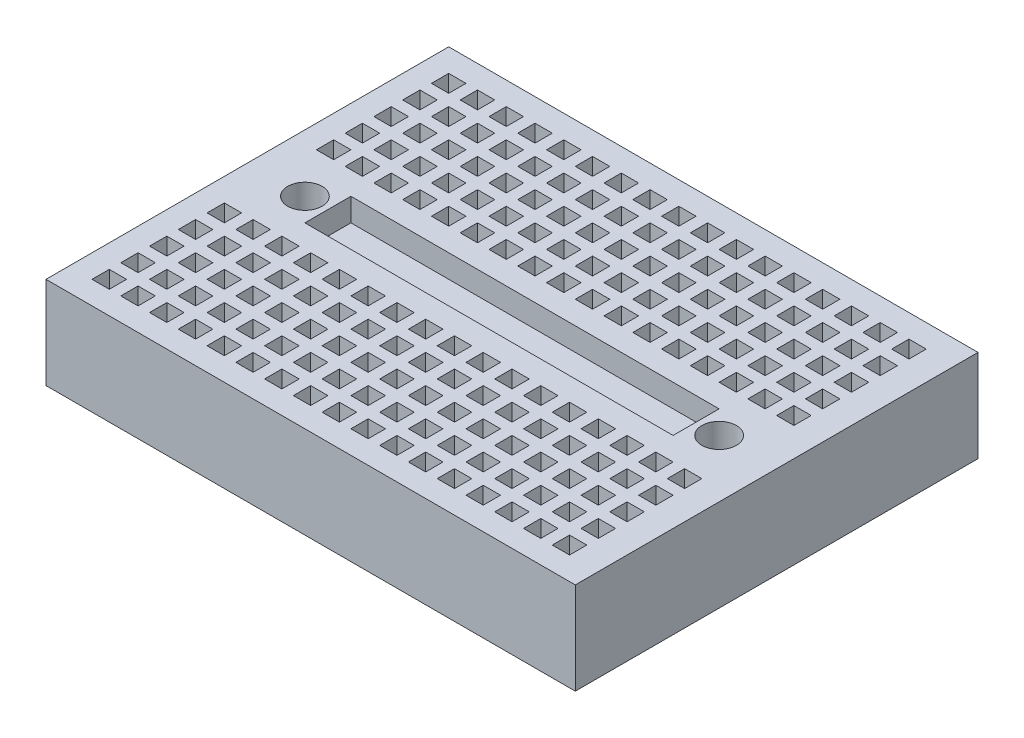
SolidWorks part; units mm, degrees
ref_plane "Front Plane" through (0, 0, 0) normal (0, 0, 1) x (1, 0, 0)
ref_plane "Top Plane" through (0, 0, 0) normal (0, 1, 0) x (1, 0, 0)
ref_plane "Right Plane" through (0, 0, 0) normal (1, 0, 0) x (0, 0, -1)
sketch "Sketch1" plane through (0, 0, 0) normal (0, 1, 0) x (1, 0, 0)
  line L1 (23, -17.5) -> (-23, -17.5)
  line L2 (23, -17.5) -> (23, 17.5)
  line L3 (23, 17.5) -> (-23, 17.5)
  line L4 (-23, -17.5) -> (-23, 17.5)
  line L5 (23, -17.5) -> (-23, 17.5) construction
  line L6 (23, 17.5) -> (-23, -17.5) construction
  circle A0 centre (18, 0) radius 1.5
  circle A1 centre (-18, 0) radius 1.5
  point P0 (0, 0)
  point P11 (-18, 0)
  dimension "D3" = 3
  dimension "D4" = 3
  dimension "D1" = 46
  dimension "D2" = 35
  dimension "D5" = 5
  dimension "D6" = 5
extrude "Boss-Extrude1" add sketch "Sketch1" along normal blind 8
sketch "Sketch2" plane through (0, 8, 0) normal (0, 1, 0) x (1, 0, 0)
  line L1 (16, -2) -> (-16, -2)
  line L2 (16, -2) -> (16, 2)
  line L3 (16, 2) -> (-16, 2)
  line L4 (-16, -2) -> (-16, 2)
  line L5 (16, -2) -> (-16, 2) construction
  line L6 (16, 2) -> (-16, -2) construction
  circle A0 centre (-18, 0) radius 1.5 construction
  point P0 (0, 0)
  dimension "D1" = 4
  dimension "D2" = 2
extrude "Cut-Extrude1" cut sketch "Sketch2" against normal blind 2
sketch "Sketch3" plane through (0, 8, 0) normal (0, 1, 0) x (1, 0, 0)
  line L0 (23, 17.5) -> (-23, 17.5) construction
  line L1 (-21, 15.5) -> (-19.5, 15.5)
  line L2 (-21, 15.5) -> (-21, 14)
  line L3 (-21, 14) -> (-19.5, 14)
  line L4 (-19.5, 15.5) -> (-19.5, 14)
  line L5 (-21, 15.5) -> (-19.5, 14) construction
  line L6 (-21, 14) -> (-19.5, 15.5) construction
  line L7 (-23, 17.5) -> (-23, -17.5) construction
  line L8 (-18.5, 15.5) -> (-17, 15.5)
  line L9 (-18.5, 15.5) -> (-18.5, 14)
  line L10 (-17, 15.5) -> (-17, 14)
  line L11 (-18.5, 14) -> (-17, 14)
  line L12 (-16, 15.5) -> (-14.5, 15.5)
  line L13 (-16, 15.5) -> (-16, 14)
  line L14 (-14.5, 15.5) -> (-14.5, 14)
  line L15 (-16, 14) -> (-14.5, 14)
  line L16 (-13.5, 15.5) -> (-12, 15.5)
  line L17 (-13.5, 15.5) -> (-13.5, 14)
  line L18 (-12, 15.5) -> (-12, 14)
  line L19 (-13.5, 14) -> (-12, 14)
  line L20 (-11, 15.5) -> (-9.5, 15.5)
  line L21 (-11, 15.5) -> (-11, 14)
  line L22 (-9.5, 15.5) -> (-9.5, 14)
  line L23 (-11, 14) -> (-9.5, 14)
  line L24 (-8.5, 15.5) -> (-7, 15.5)
  line L25 (-8.5, 15.5) -> (-8.5, 14)
  line L26 (-7, 15.5) -> (-7, 14)
  line L27 (-8.5, 14) -> (-7, 14)
  line L28 (-6, 15.5) -> (-4.5, 15.5)
  line L29 (-6, 15.5) -> (-6, 14)
  line L30 (-4.5, 15.5) -> (-4.5, 14)
  line L31 (-6, 14) -> (-4.5, 14)
  line L32 (-3.5, 15.5) -> (-2, 15.5)
  line L33 (-3.5, 15.5) -> (-3.5, 14)
  line L34 (-2, 15.5) -> (-2, 14)
  line L35 (-3.5, 14) -> (-2, 14)
  line L36 (-1, 15.5) -> (0.5, 15.5)
  line L37 (-1, 15.5) -> (-1, 14)
  line L38 (0.5, 15.5) -> (0.5, 14)
  line L39 (-1, 14) -> (0.5, 14)
  line L40 (1.5, 15.5) -> (3, 15.5)
  line L41 (1.5, 15.5) -> (1.5, 14)
  line L42 (3, 15.5) -> (3, 14)
  line L43 (1.5, 14) -> (3, 14)
  line L44 (4, 15.5) -> (5.5, 15.5)
  line L45 (4, 15.5) -> (4, 14)
  line L46 (5.5, 15.5) -> (5.5, 14)
  line L47 (4, 14) -> (5.5, 14)
  line L48 (6.5, 15.5) -> (8, 15.5)
  line L49 (6.5, 15.5) -> (6.5, 14)
  line L50 (8, 15.5) -> (8, 14)
  line L51 (6.5, 14) -> (8, 14)
  line L52 (9, 15.5) -> (10.5, 15.5)
  line L53 (9, 15.5) -> (9, 14)
  line L54 (10.5, 15.5) -> (10.5, 14)
  line L55 (9, 14) -> (10.5, 14)
  line L56 (11.5, 15.5) -> (13, 15.5)
  line L57 (11.5, 15.5) -> (11.5, 14)
  line L58 (13, 15.5) -> (13, 14)
  line L59 (11.5, 14) -> (13, 14)
  line L60 (14, 15.5) -> (15.5, 15.5)
  line L61 (14, 15.5) -> (14, 14)
  line L62 (15.5, 15.5) -> (15.5, 14)
  line L63 (14, 14) -> (15.5, 14)
  line L64 (16.5, 15.5) -> (18, 15.5)
  line L65 (16.5, 15.5) -> (16.5, 14)
  line L66 (18, 15.5) -> (18, 14)
  line L67 (16.5, 14) -> (18, 14)
  line L68 (19, 15.5) -> (20.5, 15.5)
  line L69 (19, 15.5) -> (19, 14)
  line L70 (20.5, 15.5) -> (20.5, 14)
  line L71 (19, 14) -> (20.5, 14)
  line L72 (-18.5, 13) -> (-17, 13)
  line L73 (-18.5, 13) -> (-18.5, 11.5)
  line L74 (-17, 13) -> (-17, 11.5)
  line L75 (-18.5, 11.5) -> (-17, 11.5)
  line L76 (-16, 13) -> (-14.5, 13)
  line L77 (-16, 13) -> (-16, 11.5)
  line L78 (-14.5, 13) -> (-14.5, 11.5)
  line L79 (-16, 11.5) -> (-14.5, 11.5)
  line L80 (-13.5, 13) -> (-12, 13)
  line L81 (-13.5, 13) -> (-13.5, 11.5)
  line L82 (-12, 13) -> (-12, 11.5)
  line L83 (-13.5, 11.5) -> (-12, 11.5)
  line L84 (-11, 13) -> (-9.5, 13)
  line L85 (-11, 13) -> (-11, 11.5)
  line L86 (-9.5, 13) -> (-9.5, 11.5)
  line L87 (-11, 11.5) -> (-9.5, 11.5)
  line L88 (-8.5, 13) -> (-7, 13)
  line L89 (-8.5, 13) -> (-8.5, 11.5)
  line L90 (-7, 13) -> (-7, 11.5)
  line L91 (-8.5, 11.5) -> (-7, 11.5)
  line L92 (-6, 13) -> (-4.5, 13)
  line L93 (-6, 13) -> (-6, 11.5)
  line L94 (-4.5, 13) -> (-4.5, 11.5)
  line L95 (-6, 11.5) -> (-4.5, 11.5)
  line L96 (-3.5, 13) -> (-2, 13)
  line L97 (-3.5, 13) -> (-3.5, 11.5)
  line L98 (-2, 13) -> (-2, 11.5)
  line L99 (-3.5, 11.5) -> (-2, 11.5)
  line L100 (-1, 13) -> (0.5, 13)
  line L101 (-1, 13) -> (-1, 11.5)
  line L102 (0.5, 13) -> (0.5, 11.5)
  line L103 (-1, 11.5) -> (0.5, 11.5)
  line L104 (1.5, 13) -> (3, 13)
  line L105 (1.5, 13) -> (1.5, 11.5)
  line L106 (3, 13) -> (3, 11.5)
  line L107 (1.5, 11.5) -> (3, 11.5)
  line L108 (4, 13) -> (5.5, 13)
  line L109 (4, 13) -> (4, 11.5)
  line L110 (5.5, 13) -> (5.5, 11.5)
  line L111 (4, 11.5) -> (5.5, 11.5)
  line L112 (6.5, 13) -> (8, 13)
  line L113 (6.5, 13) -> (6.5, 11.5)
  line L114 (8, 13) -> (8, 11.5)
  line L115 (6.5, 11.5) -> (8, 11.5)
  line L116 (9, 13) -> (10.5, 13)
  line L117 (9, 13) -> (9, 11.5)
  line L118 (10.5, 13) -> (10.5, 11.5)
  line L119 (9, 11.5) -> (10.5, 11.5)
  line L120 (11.5, 13) -> (13, 13)
  line L121 (11.5, 13) -> (11.5, 11.5)
  line L122 (13, 13) -> (13, 11.5)
  line L123 (11.5, 11.5) -> (13, 11.5)
  line L124 (14, 13) -> (15.5, 13)
  line L125 (14, 13) -> (14, 11.5)
  line L126 (15.5, 13) -> (15.5, 11.5)
  line L127 (14, 11.5) -> (15.5, 11.5)
  line L128 (16.5, 13) -> (18, 13)
  line L129 (16.5, 13) -> (16.5, 11.5)
  line L130 (18, 13) -> (18, 11.5)
  line L131 (16.5, 11.5) -> (18, 11.5)
  line L132 (19, 13) -> (20.5, 13)
  line L133 (19, 13) -> (19, 11.5)
  line L134 (20.5, 13) -> (20.5, 11.5)
  line L135 (19, 11.5) -> (20.5, 11.5)
  line L136 (-18.5, 10.5) -> (-17, 10.5)
  line L137 (-18.5, 10.5) -> (-18.5, 9)
  line L138 (-17, 10.5) -> (-17, 9)
  line L139 (-18.5, 9) -> (-17, 9)
  line L140 (-16, 10.5) -> (-14.5, 10.5)
  line L141 (-16, 10.5) -> (-16, 9)
  line L142 (-14.5, 10.5) -> (-14.5, 9)
  line L143 (-16, 9) -> (-14.5, 9)
  line L144 (-13.5, 10.5) -> (-12, 10.5)
  line L145 (-13.5, 10.5) -> (-13.5, 9)
  line L146 (-12, 10.5) -> (-12, 9)
  line L147 (-13.5, 9) -> (-12, 9)
  line L148 (-11, 10.5) -> (-9.5, 10.5)
  line L149 (-11, 10.5) -> (-11, 9)
  line L150 (-9.5, 10.5) -> (-9.5, 9)
  line L151 (-11, 9) -> (-9.5, 9)
  line L152 (-8.5, 10.5) -> (-7, 10.5)
  line L153 (-8.5, 10.5) -> (-8.5, 9)
  line L154 (-7, 10.5) -> (-7, 9)
  line L155 (-8.5, 9) -> (-7, 9)
  line L156 (-6, 10.5) -> (-4.5, 10.5)
  line L157 (-6, 10.5) -> (-6, 9)
  line L158 (-4.5, 10.5) -> (-4.5, 9)
  line L159 (-6, 9) -> (-4.5, 9)
  line L160 (-3.5, 10.5) -> (-2, 10.5)
  line L161 (-3.5, 10.5) -> (-3.5, 9)
  line L162 (-2, 10.5) -> (-2, 9)
  line L163 (-3.5, 9) -> (-2, 9)
  line L164 (-1, 10.5) -> (0.5, 10.5)
  line L165 (-1, 10.5) -> (-1, 9)
  line L166 (0.5, 10.5) -> (0.5, 9)
  line L167 (-1, 9) -> (0.5, 9)
  line L168 (1.5, 10.5) -> (3, 10.5)
  line L169 (1.5, 10.5) -> (1.5, 9)
  line L170 (3, 10.5) -> (3, 9)
  line L171 (1.5, 9) -> (3, 9)
  line L172 (4, 10.5) -> (5.5, 10.5)
  line L173 (4, 10.5) -> (4, 9)
  line L174 (5.5, 10.5) -> (5.5, 9)
  line L175 (4, 9) -> (5.5, 9)
  line L176 (6.5, 10.5) -> (8, 10.5)
  line L177 (6.5, 10.5) -> (6.5, 9)
  line L178 (8, 10.5) -> (8, 9)
  line L179 (6.5, 9) -> (8, 9)
  line L180 (9, 10.5) -> (10.5, 10.5)
  line L181 (9, 10.5) -> (9, 9)
  line L182 (10.5, 10.5) -> (10.5, 9)
  line L183 (9, 9) -> (10.5, 9)
  line L184 (11.5, 10.5) -> (13, 10.5)
  line L185 (11.5, 10.5) -> (11.5, 9)
  line L186 (13, 10.5) -> (13, 9)
  line L187 (11.5, 9) -> (13, 9)
  line L188 (14, 10.5) -> (15.5, 10.5)
  line L189 (14, 10.5) -> (14, 9)
  line L190 (15.5, 10.5) -> (15.5, 9)
  line L191 (14, 9) -> (15.5, 9)
  line L192 (16.5, 10.5) -> (18, 10.5)
  line L193 (16.5, 10.5) -> (16.5, 9)
  line L194 (18, 10.5) -> (18, 9)
  line L195 (16.5, 9) -> (18, 9)
  line L196 (19, 10.5) -> (20.5, 10.5)
  line L197 (19, 10.5) -> (19, 9)
  line L198 (20.5, 10.5) -> (20.5, 9)
  line L199 (19, 9) -> (20.5, 9)
  line L200 (-18.5, 8) -> (-17, 8)
  line L201 (-18.5, 8) -> (-18.5, 6.5)
  line L202 (-17, 8) -> (-17, 6.5)
  line L203 (-18.5, 6.5) -> (-17, 6.5)
  line L204 (-16, 8) -> (-14.5, 8)
  line L205 (-16, 8) -> (-16, 6.5)
  line L206 (-14.5, 8) -> (-14.5, 6.5)
  line L207 (-16, 6.5) -> (-14.5, 6.5)
  line L208 (-13.5, 8) -> (-12, 8)
  line L209 (-13.5, 8) -> (-13.5, 6.5)
  line L210 (-12, 8) -> (-12, 6.5)
  line L211 (-13.5, 6.5) -> (-12, 6.5)
  line L212 (-11, 8) -> (-9.5, 8)
  line L213 (-11, 8) -> (-11, 6.5)
  line L214 (-9.5, 8) -> (-9.5, 6.5)
  line L215 (-11, 6.5) -> (-9.5, 6.5)
  line L216 (-8.5, 8) -> (-7, 8)
  line L217 (-8.5, 8) -> (-8.5, 6.5)
  line L218 (-7, 8) -> (-7, 6.5)
  line L219 (-8.5, 6.5) -> (-7, 6.5)
  line L220 (-6, 8) -> (-4.5, 8)
  line L221 (-6, 8) -> (-6, 6.5)
  line L222 (-4.5, 8) -> (-4.5, 6.5)
  line L223 (-6, 6.5) -> (-4.5, 6.5)
  line L224 (-3.5, 8) -> (-2, 8)
  line L225 (-3.5, 8) -> (-3.5, 6.5)
  line L226 (-2, 8) -> (-2, 6.5)
  line L227 (-3.5, 6.5) -> (-2, 6.5)
  line L228 (-1, 8) -> (0.5, 8)
  line L229 (-1, 8) -> (-1, 6.5)
  line L230 (0.5, 8) -> (0.5, 6.5)
  line L231 (-1, 6.5) -> (0.5, 6.5)
  line L232 (1.5, 8) -> (3, 8)
  line L233 (1.5, 8) -> (1.5, 6.5)
  line L234 (3, 8) -> (3, 6.5)
  line L235 (1.5, 6.5) -> (3, 6.5)
  line L236 (4, 8) -> (5.5, 8)
  line L237 (4, 8) -> (4, 6.5)
  line L238 (5.5, 8) -> (5.5, 6.5)
  line L239 (4, 6.5) -> (5.5, 6.5)
  line L240 (6.5, 8) -> (8, 8)
  line L241 (6.5, 8) -> (6.5, 6.5)
  line L242 (8, 8) -> (8, 6.5)
  line L243 (6.5, 6.5) -> (8, 6.5)
  line L244 (9, 8) -> (10.5, 8)
  line L245 (9, 8) -> (9, 6.5)
  line L246 (10.5, 8) -> (10.5, 6.5)
  line L247 (9, 6.5) -> (10.5, 6.5)
  line L248 (11.5, 8) -> (13, 8)
  line L249 (11.5, 8) -> (11.5, 6.5)
  line L250 (13, 8) -> (13, 6.5)
  line L251 (11.5, 6.5) -> (13, 6.5)
  line L252 (14, 8) -> (15.5, 8)
  line L253 (14, 8) -> (14, 6.5)
  line L254 (15.5, 8) -> (15.5, 6.5)
  line L255 (14, 6.5) -> (15.5, 6.5)
  line L256 (16.5, 8) -> (18, 8)
  line L257 (16.5, 8) -> (16.5, 6.5)
  line L258 (18, 8) -> (18, 6.5)
  line L259 (16.5, 6.5) -> (18, 6.5)
  line L260 (19, 8) -> (20.5, 8)
  line L261 (19, 8) -> (19, 6.5)
  line L262 (20.5, 8) -> (20.5, 6.5)
  line L263 (19, 6.5) -> (20.5, 6.5)
  line L264 (-18.5, 5.5) -> (-17, 5.5)
  line L265 (-18.5, 5.5) -> (-18.5, 4)
  line L266 (-17, 5.5) -> (-17, 4)
  line L267 (-18.5, 4) -> (-17, 4)
  line L268 (-16, 5.5) -> (-14.5, 5.5)
  line L269 (-16, 5.5) -> (-16, 4)
  line L270 (-14.5, 5.5) -> (-14.5, 4)
  line L271 (-16, 4) -> (-14.5, 4)
  line L272 (-13.5, 5.5) -> (-12, 5.5)
  line L273 (-13.5, 5.5) -> (-13.5, 4)
  line L274 (-12, 5.5) -> (-12, 4)
  line L275 (-13.5, 4) -> (-12, 4)
  line L276 (-11, 5.5) -> (-9.5, 5.5)
  line L277 (-11, 5.5) -> (-11, 4)
  line L278 (-9.5, 5.5) -> (-9.5, 4)
  line L279 (-11, 4) -> (-9.5, 4)
  line L280 (-8.5, 5.5) -> (-7, 5.5)
  line L281 (-8.5, 5.5) -> (-8.5, 4)
  line L282 (-7, 5.5) -> (-7, 4)
  line L283 (-8.5, 4) -> (-7, 4)
  line L284 (-6, 5.5) -> (-4.5, 5.5)
  line L285 (-6, 5.5) -> (-6, 4)
  line L286 (-4.5, 5.5) -> (-4.5, 4)
  line L287 (-6, 4) -> (-4.5, 4)
  line L288 (-3.5, 5.5) -> (-2, 5.5)
  line L289 (-3.5, 5.5) -> (-3.5, 4)
  line L290 (-2, 5.5) -> (-2, 4)
  line L291 (-3.5, 4) -> (-2, 4)
  line L292 (-1, 5.5) -> (0.5, 5.5)
  line L293 (-1, 5.5) -> (-1, 4)
  line L294 (0.5, 5.5) -> (0.5, 4)
  line L295 (-1, 4) -> (0.5, 4)
  line L296 (1.5, 5.5) -> (3, 5.5)
  line L297 (1.5, 5.5) -> (1.5, 4)
  line L298 (3, 5.5) -> (3, 4)
  line L299 (1.5, 4) -> (3, 4)
  line L300 (4, 5.5) -> (5.5, 5.5)
  line L301 (4, 5.5) -> (4, 4)
  line L302 (5.5, 5.5) -> (5.5, 4)
  line L303 (4, 4) -> (5.5, 4)
  line L304 (6.5, 5.5) -> (8, 5.5)
  line L305 (6.5, 5.5) -> (6.5, 4)
  line L306 (8, 5.5) -> (8, 4)
  line L307 (6.5, 4) -> (8, 4)
  line L308 (9, 5.5) -> (10.5, 5.5)
  line L309 (9, 5.5) -> (9, 4)
  line L310 (10.5, 5.5) -> (10.5, 4)
  line L311 (9, 4) -> (10.5, 4)
  line L312 (11.5, 5.5) -> (13, 5.5)
  line L313 (11.5, 5.5) -> (11.5, 4)
  line L314 (13, 5.5) -> (13, 4)
  line L315 (11.5, 4) -> (13, 4)
  line L316 (14, 5.5) -> (15.5, 5.5)
  line L317 (14, 5.5) -> (14, 4)
  line L318 (15.5, 5.5) -> (15.5, 4)
  line L319 (14, 4) -> (15.5, 4)
  line L320 (16.5, 5.5) -> (18, 5.5)
  line L321 (16.5, 5.5) -> (16.5, 4)
  line L322 (18, 5.5) -> (18, 4)
  line L323 (16.5, 4) -> (18, 4)
  line L324 (19, 5.5) -> (20.5, 5.5)
  line L325 (19, 5.5) -> (19, 4)
  line L326 (20.5, 5.5) -> (20.5, 4)
  line L327 (19, 4) -> (20.5, 4)
  line L328 (-21, 13) -> (-19.5, 13)
  line L329 (-21, 13) -> (-21, 11.5)
  line L330 (-19.5, 13) -> (-19.5, 11.5)
  line L331 (-21, 11.5) -> (-19.5, 11.5)
  line L332 (-21, 10.5) -> (-19.5, 10.5)
  line L333 (-21, 10.5) -> (-21, 9)
  line L334 (-19.5, 10.5) -> (-19.5, 9)
  line L335 (-21, 9) -> (-19.5, 9)
  line L336 (-21, 8) -> (-19.5, 8)
  line L337 (-21, 8) -> (-21, 6.5)
  line L338 (-19.5, 8) -> (-19.5, 6.5)
  line L339 (-21, 6.5) -> (-19.5, 6.5)
  line L340 (-21, 5.5) -> (-19.5, 5.5)
  line L341 (-21, 5.5) -> (-21, 4)
  line L342 (-19.5, 5.5) -> (-19.5, 4)
  line L343 (-21, 4) -> (-19.5, 4)
  line L344 (-23, 0) -> (23, 0) construction
  line L345 (23, -17.5) -> (23, 17.5) construction
  line L346 (-21, -14) -> (-19.5, -15.5) construction
  line L347 (-21, -15.5) -> (-19.5, -14) construction
  line L348 (-21, -4) -> (-19.5, -4)
  line L349 (-19.5, -5.5) -> (-19.5, -4)
  line L350 (-21, -5.5) -> (-21, -4)
  line L351 (-21, -5.5) -> (-19.5, -5.5)
  line L352 (-21, -6.5) -> (-19.5, -6.5)
  line L353 (-19.5, -8) -> (-19.5, -6.5)
  line L354 (-21, -8) -> (-21, -6.5)
  line L355 (-21, -8) -> (-19.5, -8)
  line L356 (-21, -9) -> (-19.5, -9)
  line L357 (-19.5, -10.5) -> (-19.5, -9)
  line L358 (-21, -10.5) -> (-21, -9)
  line L359 (-21, -10.5) -> (-19.5, -10.5)
  line L360 (-21, -11.5) -> (-19.5, -11.5)
  line L361 (-19.5, -13) -> (-19.5, -11.5)
  line L362 (-21, -13) -> (-21, -11.5)
  line L363 (-21, -13) -> (-19.5, -13)
  line L364 (19, -4) -> (20.5, -4)
  line L365 (20.5, -5.5) -> (20.5, -4)
  line L366 (19, -5.5) -> (19, -4)
  line L367 (19, -5.5) -> (20.5, -5.5)
  line L368 (16.5, -4) -> (18, -4)
  line L369 (18, -5.5) -> (18, -4)
  line L370 (16.5, -5.5) -> (16.5, -4)
  line L371 (16.5, -5.5) -> (18, -5.5)
  line L372 (14, -4) -> (15.5, -4)
  line L373 (15.5, -5.5) -> (15.5, -4)
  line L374 (14, -5.5) -> (14, -4)
  line L375 (14, -5.5) -> (15.5, -5.5)
  line L376 (11.5, -4) -> (13, -4)
  line L377 (13, -5.5) -> (13, -4)
  line L378 (11.5, -5.5) -> (11.5, -4)
  line L379 (11.5, -5.5) -> (13, -5.5)
  line L380 (9, -4) -> (10.5, -4)
  line L381 (10.5, -5.5) -> (10.5, -4)
  line L382 (9, -5.5) -> (9, -4)
  line L383 (9, -5.5) -> (10.5, -5.5)
  line L384 (6.5, -4) -> (8, -4)
  line L385 (8, -5.5) -> (8, -4)
  line L386 (6.5, -5.5) -> (6.5, -4)
  line L387 (6.5, -5.5) -> (8, -5.5)
  line L388 (4, -4) -> (5.5, -4)
  line L389 (5.5, -5.5) -> (5.5, -4)
  line L390 (4, -5.5) -> (4, -4)
  line L391 (4, -5.5) -> (5.5, -5.5)
  line L392 (1.5, -4) -> (3, -4)
  line L393 (3, -5.5) -> (3, -4)
  line L394 (1.5, -5.5) -> (1.5, -4)
  line L395 (1.5, -5.5) -> (3, -5.5)
  line L396 (-1, -4) -> (0.5, -4)
  line L397 (0.5, -5.5) -> (0.5, -4)
  line L398 (-1, -5.5) -> (-1, -4)
  line L399 (-1, -5.5) -> (0.5, -5.5)
  line L400 (-3.5, -4) -> (-2, -4)
  line L401 (-2, -5.5) -> (-2, -4)
  line L402 (-3.5, -5.5) -> (-3.5, -4)
  line L403 (-3.5, -5.5) -> (-2, -5.5)
  line L404 (-6, -4) -> (-4.5, -4)
  line L405 (-4.5, -5.5) -> (-4.5, -4)
  line L406 (-6, -5.5) -> (-6, -4)
  line L407 (-6, -5.5) -> (-4.5, -5.5)
  line L408 (-8.5, -4) -> (-7, -4)
  line L409 (-7, -5.5) -> (-7, -4)
  line L410 (-8.5, -5.5) -> (-8.5, -4)
  line L411 (-8.5, -5.5) -> (-7, -5.5)
  line L412 (-11, -4) -> (-9.5, -4)
  line L413 (-9.5, -5.5) -> (-9.5, -4)
  line L414 (-11, -5.5) -> (-11, -4)
  line L415 (-11, -5.5) -> (-9.5, -5.5)
  line L416 (-13.5, -4) -> (-12, -4)
  line L417 (-12, -5.5) -> (-12, -4)
  line L418 (-13.5, -5.5) -> (-13.5, -4)
  line L419 (-13.5, -5.5) -> (-12, -5.5)
  line L420 (-16, -4) -> (-14.5, -4)
  line L421 (-14.5, -5.5) -> (-14.5, -4)
  line L422 (-16, -5.5) -> (-16, -4)
  line L423 (-16, -5.5) -> (-14.5, -5.5)
  line L424 (-18.5, -4) -> (-17, -4)
  line L425 (-17, -5.5) -> (-17, -4)
  line L426 (-18.5, -5.5) -> (-18.5, -4)
  line L427 (-18.5, -5.5) -> (-17, -5.5)
  line L428 (19, -6.5) -> (20.5, -6.5)
  line L429 (20.5, -8) -> (20.5, -6.5)
  line L430 (19, -8) -> (19, -6.5)
  line L431 (19, -8) -> (20.5, -8)
  line L432 (16.5, -6.5) -> (18, -6.5)
  line L433 (18, -8) -> (18, -6.5)
  line L434 (16.5, -8) -> (16.5, -6.5)
  line L435 (16.5, -8) -> (18, -8)
  line L436 (14, -6.5) -> (15.5, -6.5)
  line L437 (15.5, -8) -> (15.5, -6.5)
  line L438 (14, -8) -> (14, -6.5)
  line L439 (14, -8) -> (15.5, -8)
  line L440 (11.5, -6.5) -> (13, -6.5)
  line L441 (13, -8) -> (13, -6.5)
  line L442 (11.5, -8) -> (11.5, -6.5)
  line L443 (11.5, -8) -> (13, -8)
  line L444 (9, -6.5) -> (10.5, -6.5)
  line L445 (10.5, -8) -> (10.5, -6.5)
  line L446 (9, -8) -> (9, -6.5)
  line L447 (9, -8) -> (10.5, -8)
  line L448 (6.5, -6.5) -> (8, -6.5)
  line L449 (8, -8) -> (8, -6.5)
  line L450 (6.5, -8) -> (6.5, -6.5)
  line L451 (6.5, -8) -> (8, -8)
  line L452 (4, -6.5) -> (5.5, -6.5)
  line L453 (5.5, -8) -> (5.5, -6.5)
  line L454 (4, -8) -> (4, -6.5)
  line L455 (4, -8) -> (5.5, -8)
  line L456 (1.5, -6.5) -> (3, -6.5)
  line L457 (3, -8) -> (3, -6.5)
  line L458 (1.5, -8) -> (1.5, -6.5)
  line L459 (1.5, -8) -> (3, -8)
  line L460 (-1, -6.5) -> (0.5, -6.5)
  line L461 (0.5, -8) -> (0.5, -6.5)
  line L462 (-1, -8) -> (-1, -6.5)
  line L463 (-1, -8) -> (0.5, -8)
  line L464 (-3.5, -6.5) -> (-2, -6.5)
  line L465 (-2, -8) -> (-2, -6.5)
  line L466 (-3.5, -8) -> (-3.5, -6.5)
  line L467 (-3.5, -8) -> (-2, -8)
  line L468 (-6, -6.5) -> (-4.5, -6.5)
  line L469 (-4.5, -8) -> (-4.5, -6.5)
  line L470 (-6, -8) -> (-6, -6.5)
  line L471 (-6, -8) -> (-4.5, -8)
  line L472 (-8.5, -6.5) -> (-7, -6.5)
  line L473 (-7, -8) -> (-7, -6.5)
  line L474 (-8.5, -8) -> (-8.5, -6.5)
  line L475 (-8.5, -8) -> (-7, -8)
  line L476 (-11, -6.5) -> (-9.5, -6.5)
  line L477 (-9.5, -8) -> (-9.5, -6.5)
  line L478 (-11, -8) -> (-11, -6.5)
  line L479 (-11, -8) -> (-9.5, -8)
  line L480 (-13.5, -6.5) -> (-12, -6.5)
  line L481 (-12, -8) -> (-12, -6.5)
  line L482 (-13.5, -8) -> (-13.5, -6.5)
  line L483 (-13.5, -8) -> (-12, -8)
  line L484 (-16, -6.5) -> (-14.5, -6.5)
  line L485 (-14.5, -8) -> (-14.5, -6.5)
  line L486 (-16, -8) -> (-16, -6.5)
  line L487 (-16, -8) -> (-14.5, -8)
  line L488 (-18.5, -6.5) -> (-17, -6.5)
  line L489 (-17, -8) -> (-17, -6.5)
  line L490 (-18.5, -8) -> (-18.5, -6.5)
  line L491 (-18.5, -8) -> (-17, -8)
  line L492 (19, -9) -> (20.5, -9)
  line L493 (20.5, -10.5) -> (20.5, -9)
  line L494 (19, -10.5) -> (19, -9)
  line L495 (19, -10.5) -> (20.5, -10.5)
  line L496 (16.5, -9) -> (18, -9)
  line L497 (18, -10.5) -> (18, -9)
  line L498 (16.5, -10.5) -> (16.5, -9)
  line L499 (16.5, -10.5) -> (18, -10.5)
  line L500 (14, -9) -> (15.5, -9)
  line L501 (15.5, -10.5) -> (15.5, -9)
  line L502 (14, -10.5) -> (14, -9)
  line L503 (14, -10.5) -> (15.5, -10.5)
  line L504 (11.5, -9) -> (13, -9)
  line L505 (13, -10.5) -> (13, -9)
  line L506 (11.5, -10.5) -> (11.5, -9)
  line L507 (11.5, -10.5) -> (13, -10.5)
  line L508 (9, -9) -> (10.5, -9)
  line L509 (10.5, -10.5) -> (10.5, -9)
  line L510 (9, -10.5) -> (9, -9)
  line L511 (9, -10.5) -> (10.5, -10.5)
  line L512 (6.5, -9) -> (8, -9)
  line L513 (8, -10.5) -> (8, -9)
  line L514 (6.5, -10.5) -> (6.5, -9)
  line L515 (6.5, -10.5) -> (8, -10.5)
  line L516 (4, -9) -> (5.5, -9)
  line L517 (5.5, -10.5) -> (5.5, -9)
  line L518 (4, -10.5) -> (4, -9)
  line L519 (4, -10.5) -> (5.5, -10.5)
  line L520 (1.5, -9) -> (3, -9)
  line L521 (3, -10.5) -> (3, -9)
  line L522 (1.5, -10.5) -> (1.5, -9)
  line L523 (1.5, -10.5) -> (3, -10.5)
  line L524 (-1, -9) -> (0.5, -9)
  line L525 (0.5, -10.5) -> (0.5, -9)
  line L526 (-1, -10.5) -> (-1, -9)
  line L527 (-1, -10.5) -> (0.5, -10.5)
  line L528 (-3.5, -9) -> (-2, -9)
  line L529 (-2, -10.5) -> (-2, -9)
  line L530 (-3.5, -10.5) -> (-3.5, -9)
  line L531 (-3.5, -10.5) -> (-2, -10.5)
  line L532 (-6, -9) -> (-4.5, -9)
  line L533 (-4.5, -10.5) -> (-4.5, -9)
  line L534 (-6, -10.5) -> (-6, -9)
  line L535 (-6, -10.5) -> (-4.5, -10.5)
  line L536 (-8.5, -9) -> (-7, -9)
  line L537 (-7, -10.5) -> (-7, -9)
  line L538 (-8.5, -10.5) -> (-8.5, -9)
  line L539 (-8.5, -10.5) -> (-7, -10.5)
  line L540 (-11, -9) -> (-9.5, -9)
  line L541 (-9.5, -10.5) -> (-9.5, -9)
  line L542 (-11, -10.5) -> (-11, -9)
  line L543 (-11, -10.5) -> (-9.5, -10.5)
  line L544 (-13.5, -9) -> (-12, -9)
  line L545 (-12, -10.5) -> (-12, -9)
  line L546 (-13.5, -10.5) -> (-13.5, -9)
  line L547 (-13.5, -10.5) -> (-12, -10.5)
  line L548 (-16, -9) -> (-14.5, -9)
  line L549 (-14.5, -10.5) -> (-14.5, -9)
  line L550 (-16, -10.5) -> (-16, -9)
  line L551 (-16, -10.5) -> (-14.5, -10.5)
  line L552 (-18.5, -9) -> (-17, -9)
  line L553 (-17, -10.5) -> (-17, -9)
  line L554 (-18.5, -10.5) -> (-18.5, -9)
  line L555 (-18.5, -10.5) -> (-17, -10.5)
  line L556 (19, -11.5) -> (20.5, -11.5)
  line L557 (20.5, -13) -> (20.5, -11.5)
  line L558 (19, -13) -> (19, -11.5)
  line L559 (19, -13) -> (20.5, -13)
  line L560 (16.5, -11.5) -> (18, -11.5)
  line L561 (18, -13) -> (18, -11.5)
  line L562 (16.5, -13) -> (16.5, -11.5)
  line L563 (16.5, -13) -> (18, -13)
  line L564 (14, -11.5) -> (15.5, -11.5)
  line L565 (15.5, -13) -> (15.5, -11.5)
  line L566 (14, -13) -> (14, -11.5)
  line L567 (14, -13) -> (15.5, -13)
  line L568 (11.5, -11.5) -> (13, -11.5)
  line L569 (13, -13) -> (13, -11.5)
  line L570 (11.5, -13) -> (11.5, -11.5)
  line L571 (11.5, -13) -> (13, -13)
  line L572 (9, -11.5) -> (10.5, -11.5)
  line L573 (10.5, -13) -> (10.5, -11.5)
  line L574 (9, -13) -> (9, -11.5)
  line L575 (9, -13) -> (10.5, -13)
  line L576 (6.5, -11.5) -> (8, -11.5)
  line L577 (8, -13) -> (8, -11.5)
  line L578 (6.5, -13) -> (6.5, -11.5)
  line L579 (6.5, -13) -> (8, -13)
  line L580 (4, -11.5) -> (5.5, -11.5)
  line L581 (5.5, -13) -> (5.5, -11.5)
  line L582 (4, -13) -> (4, -11.5)
  line L583 (4, -13) -> (5.5, -13)
  line L584 (1.5, -11.5) -> (3, -11.5)
  line L585 (3, -13) -> (3, -11.5)
  line L586 (1.5, -13) -> (1.5, -11.5)
  line L587 (1.5, -13) -> (3, -13)
  line L588 (-1, -11.5) -> (0.5, -11.5)
  line L589 (0.5, -13) -> (0.5, -11.5)
  line L590 (-1, -13) -> (-1, -11.5)
  line L591 (-1, -13) -> (0.5, -13)
  line L592 (-3.5, -11.5) -> (-2, -11.5)
  line L593 (-2, -13) -> (-2, -11.5)
  line L594 (-3.5, -13) -> (-3.5, -11.5)
  line L595 (-3.5, -13) -> (-2, -13)
  line L596 (-6, -11.5) -> (-4.5, -11.5)
  line L597 (-4.5, -13) -> (-4.5, -11.5)
  line L598 (-6, -13) -> (-6, -11.5)
  line L599 (-6, -13) -> (-4.5, -13)
  line L600 (-8.5, -11.5) -> (-7, -11.5)
  line L601 (-7, -13) -> (-7, -11.5)
  line L602 (-8.5, -13) -> (-8.5, -11.5)
  line L603 (-8.5, -13) -> (-7, -13)
  line L604 (-11, -11.5) -> (-9.5, -11.5)
  line L605 (-9.5, -13) -> (-9.5, -11.5)
  line L606 (-11, -13) -> (-11, -11.5)
  line L607 (-11, -13) -> (-9.5, -13)
  line L608 (-13.5, -11.5) -> (-12, -11.5)
  line L609 (-12, -13) -> (-12, -11.5)
  line L610 (-13.5, -13) -> (-13.5, -11.5)
  line L611 (-13.5, -13) -> (-12, -13)
  line L612 (-16, -11.5) -> (-14.5, -11.5)
  line L613 (-14.5, -13) -> (-14.5, -11.5)
  line L614 (-16, -13) -> (-16, -11.5)
  line L615 (-16, -13) -> (-14.5, -13)
  line L616 (-18.5, -11.5) -> (-17, -11.5)
  line L617 (-17, -13) -> (-17, -11.5)
  line L618 (-18.5, -13) -> (-18.5, -11.5)
  line L619 (-18.5, -13) -> (-17, -13)
  line L620 (19, -14) -> (20.5, -14)
  line L621 (20.5, -15.5) -> (20.5, -14)
  line L622 (19, -15.5) -> (19, -14)
  line L623 (19, -15.5) -> (20.5, -15.5)
  line L624 (16.5, -14) -> (18, -14)
  line L625 (18, -15.5) -> (18, -14)
  line L626 (16.5, -15.5) -> (16.5, -14)
  line L627 (16.5, -15.5) -> (18, -15.5)
  line L628 (14, -14) -> (15.5, -14)
  line L629 (15.5, -15.5) -> (15.5, -14)
  line L630 (14, -15.5) -> (14, -14)
  line L631 (14, -15.5) -> (15.5, -15.5)
  line L632 (11.5, -14) -> (13, -14)
  line L633 (13, -15.5) -> (13, -14)
  line L634 (11.5, -15.5) -> (11.5, -14)
  line L635 (11.5, -15.5) -> (13, -15.5)
  line L636 (9, -14) -> (10.5, -14)
  line L637 (10.5, -15.5) -> (10.5, -14)
  line L638 (9, -15.5) -> (9, -14)
  line L639 (9, -15.5) -> (10.5, -15.5)
  line L640 (6.5, -14) -> (8, -14)
  line L641 (8, -15.5) -> (8, -14)
  line L642 (6.5, -15.5) -> (6.5, -14)
  line L643 (6.5, -15.5) -> (8, -15.5)
  line L644 (4, -14) -> (5.5, -14)
  line L645 (5.5, -15.5) -> (5.5, -14)
  line L646 (4, -15.5) -> (4, -14)
  line L647 (4, -15.5) -> (5.5, -15.5)
  line L648 (1.5, -14) -> (3, -14)
  line L649 (3, -15.5) -> (3, -14)
  line L650 (1.5, -15.5) -> (1.5, -14)
  line L651 (1.5, -15.5) -> (3, -15.5)
  line L652 (-1, -14) -> (0.5, -14)
  line L653 (0.5, -15.5) -> (0.5, -14)
  line L654 (-1, -15.5) -> (-1, -14)
  line L655 (-1, -15.5) -> (0.5, -15.5)
  line L656 (-3.5, -14) -> (-2, -14)
  line L657 (-2, -15.5) -> (-2, -14)
  line L658 (-3.5, -15.5) -> (-3.5, -14)
  line L659 (-3.5, -15.5) -> (-2, -15.5)
  line L660 (-6, -14) -> (-4.5, -14)
  line L661 (-4.5, -15.5) -> (-4.5, -14)
  line L662 (-6, -15.5) -> (-6, -14)
  line L663 (-6, -15.5) -> (-4.5, -15.5)
  line L664 (-8.5, -14) -> (-7, -14)
  line L665 (-7, -15.5) -> (-7, -14)
  line L666 (-8.5, -15.5) -> (-8.5, -14)
  line L667 (-8.5, -15.5) -> (-7, -15.5)
  line L668 (-11, -14) -> (-9.5, -14)
  line L669 (-9.5, -15.5) -> (-9.5, -14)
  line L670 (-11, -15.5) -> (-11, -14)
  line L671 (-11, -15.5) -> (-9.5, -15.5)
  line L672 (-13.5, -14) -> (-12, -14)
  line L673 (-12, -15.5) -> (-12, -14)
  line L674 (-13.5, -15.5) -> (-13.5, -14)
  line L675 (-13.5, -15.5) -> (-12, -15.5)
  line L676 (-16, -14) -> (-14.5, -14)
  line L677 (-14.5, -15.5) -> (-14.5, -14)
  line L678 (-16, -15.5) -> (-16, -14)
  line L679 (-16, -15.5) -> (-14.5, -15.5)
  line L680 (-18.5, -14) -> (-17, -14)
  line L681 (-17, -15.5) -> (-17, -14)
  line L682 (-18.5, -15.5) -> (-18.5, -14)
  line L683 (-18.5, -15.5) -> (-17, -15.5)
  line L684 (-19.5, -15.5) -> (-19.5, -14)
  line L685 (-21, -14) -> (-19.5, -14)
  line L686 (-21, -15.5) -> (-21, -14)
  line L687 (-21, -15.5) -> (-19.5, -15.5)
  point P0 (-20.25, 14.75)
  point P689 (-20.25, -14.75)
  dimension "D1" = 1.5
  dimension "D2" = 2
  dimension "D3" = 2
  dimension "D4" = 1.5
  dimension "D5" = 17
  dimension "D6" = 5
extrude "Cut-Extrude2" cut sketch "Sketch3" against normal blind 7
